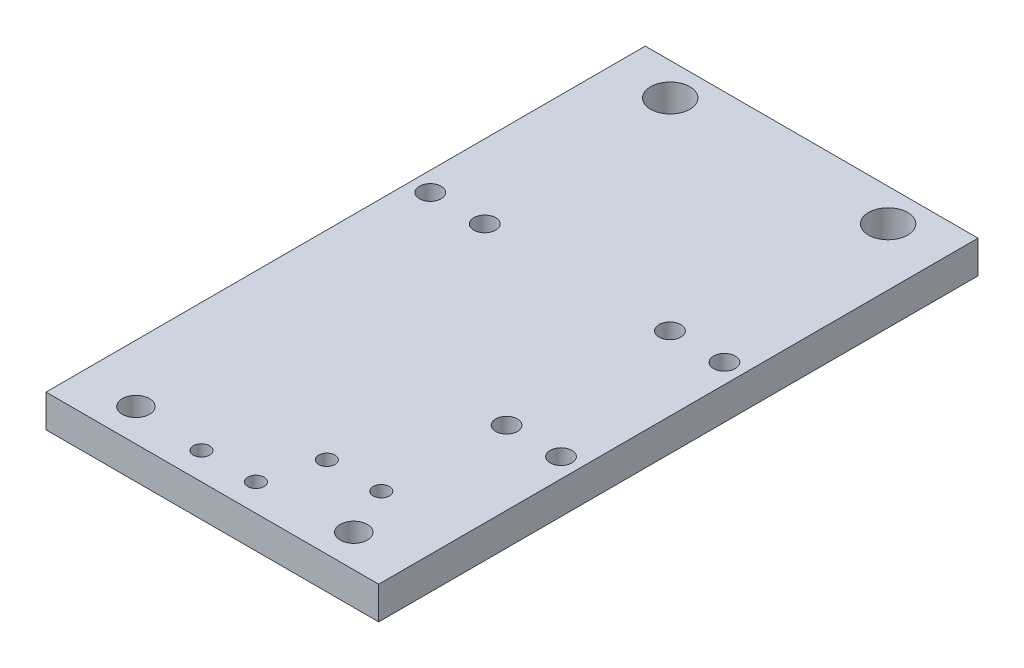
SolidWorks part; units mm, degrees
ref_plane "Front Plane" through (0, 0, 0) normal (0, 0, 1) x (1, 0, 0)
ref_plane "Top Plane" through (0, 0, 0) normal (0, 1, 0) x (1, 0, 0)
ref_plane "Right Plane" through (0, 0, 0) normal (1, 0, 0) x (0, 0, -1)
sketch "Sketch1" plane through (0, 0, 0) normal (0, 1, 0) x (1, 0, 0)
  line L0 (-30.5418, 29.2) -> (30.5418, 29.2) construction
  line L1 (-30.5418, -55.0162) -> (30.5418, -55.0162)
  line L2 (30.5418, 55.0162) -> (-30.5418, 55.0162)
  line L3 (-30.5418, 29.2) -> (-30.5418, 55.0162)
  line L4 (30.5418, -55.0162) -> (30.5418, 55.0162)
  line L5 (-30.5418, -55.0162) -> (30.5418, 55.0162) construction
  line L6 (0, 49.05) -> (-20, 49.05) construction
  line L7 (-30.5418, -29.2) -> (30.5418, -29.2) construction
  line L8 (0, 29.2) -> (0, -29.2) construction
  line L9 (0, 29.2) -> (0, 49.05) construction
  line L10 (-27, 12) -> (-17, 12) construction
  line L11 (0, 49.05) -> (20, 49.05) construction
  line L12 (0, -29.2) -> (0, -49.05) construction
  line L13 (0, -49.05) -> (20, -49.05) construction
  line L14 (0, -49.05) -> (-20, -49.05) construction
  line L15 (17, -18) -> (27, -18) construction
  line L16 (-30.5418, 29.2) -> (-30.5418, -55.0162)
  line L17 (17, -18) -> (17, 12) construction
  line L18 (17, 12) -> (27, 12) construction
  line L19 (27, -18) -> (27, 12) construction
  line L20 (27, 12) -> (30.5418, 12) construction
  line L21 (-27, 12) -> (-30.5418, 12) construction
  circle A0 centre (-20, 49.05) radius 3.6
  circle A1 centre (20, 49.05) radius 3.6
  circle A2 centre (-20, -49.05) radius 2.5
  circle A3 centre (20, -49.05) radius 2.5
  circle A4 centre (17, 12) radius 2
  circle A5 centre (27, 12) radius 2
  circle A6 centre (27, -18) radius 2
  circle A7 centre (17, -18) radius 2
  circle A8 centre (-7, -50.0162) radius 1.5
  circle A9 centre (3, -50.0162) radius 1.5
  circle A10 centre (-27, 12) radius 2
  circle A11 centre (-17, 12) radius 2
  circle A12 centre (6, -40) radius 1.5
  circle A13 centre (16, -40) radius 1.5
  point P0 (0, 0)
  point P14 (0, 0)
  dimension "D5" = 10
  dimension "D6" = 5
  dimension "D3" = 7.2
  dimension "D7" = 4
  dimension "D11" = 3
  dimension "D17" = 3
  dimension "D1" = 58.4
  dimension "D2" = 19.85
  dimension "D4" = 30
  dimension "D8" = 27
  dimension "D9" = 12
  dimension "D10" = 20
  dimension "D12" = 10
  dimension "D13" = 5
  dimension "D14" = 110.0324
  dimension "D15" = 3
  dimension "D16" = 10
  dimension "D18" = 6
  dimension "D19" = 40
extrude "Boss-Extrude1" add sketch "Sketch1" along normal blind 6 contours L4 L2 L3 L16 L1
extrude "Cut-Extrude1" cut sketch "Sketch1<3>" along normal blind 6 contours A2 | A3 | A1 | A0 | A4 | A5 | A6 | A7 | A8 | A9 | A10 | A11 | A12 | A13
sketch "Sketch1<3>" plane through (0, 0, 0) normal (0, 1, 0) x (1, 0, 0) same geometry as "Sketch1"
